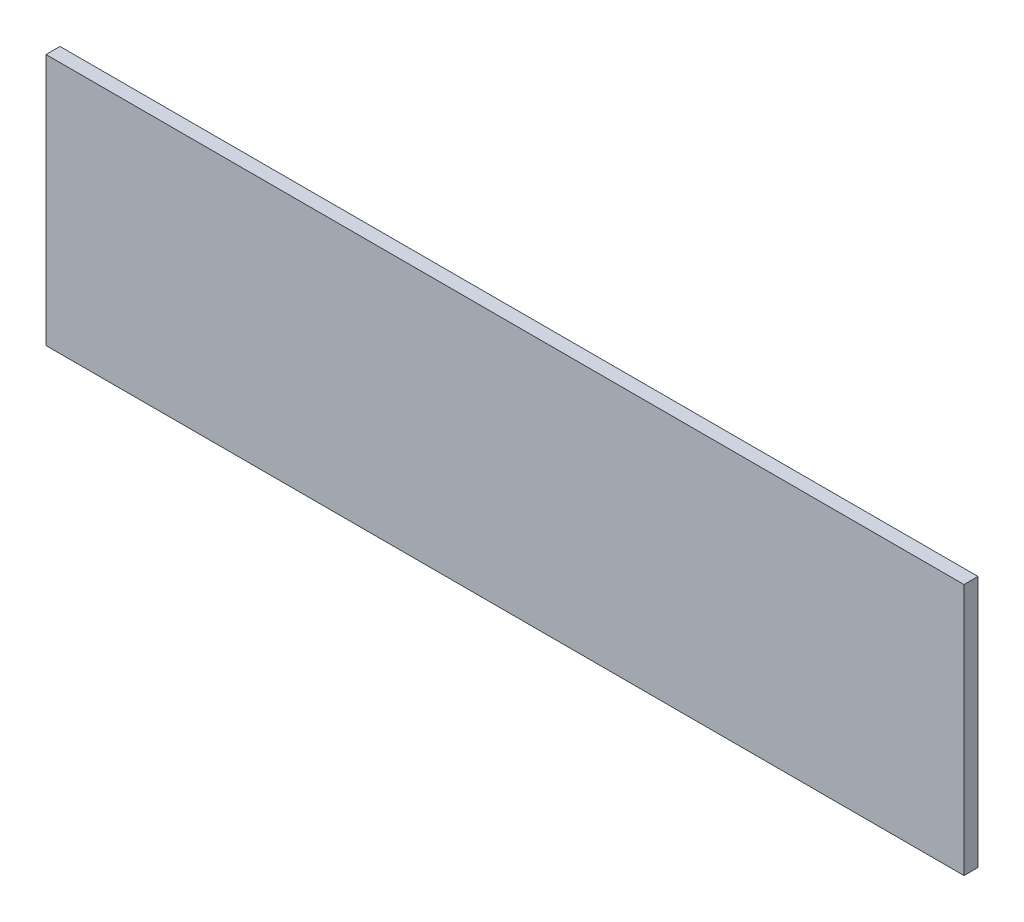
SolidWorks part; units mm, degrees
ref_plane "Front Plane" through (0, 0, 0) normal (0, 0, 1) x (1, 0, 0)
ref_plane "Top Plane" through (0, 0, 0) normal (0, 1, 0) x (1, 0, 0)
ref_plane "Right Plane" through (0, 0, 0) normal (1, 0, 0) x (0, 0, -1)
sketch "Sketch1" plane through (0, 0, 0) normal (0, 0, 1) x (1, 0, 0)
  line L1 (147.5, -40.5) -> (-147.5, -40.5)
  line L2 (147.5, -40.5) -> (147.5, 40.5)
  line L3 (147.5, 40.5) -> (-147.5, 40.5)
  line L4 (-147.5, -40.5) -> (-147.5, 40.5)
  line L5 (147.5, -40.5) -> (-147.5, 40.5) construction
  line L6 (147.5, 40.5) -> (-147.5, -40.5) construction
  point P0 (0, 0)
  dimension "D1" = 295
  dimension "D2" = 81
extrude "Boss-Extrude1" add sketch "Sketch1" along normal blind 4.5
sketch "Sketch2" plane through (0, 0, 4.5) normal (0, 0, 1) x (1, 0, 0)
  line L0 (-147.5, 40.5) -> (-143, 36) construction
  line L1 (-147.5, 40.5) -> (-143, 40.5) construction
  line L2 (-147.5, 40.5) -> (-147.5, 36) construction
  line L3 (-147.5, 36) -> (-143, 36) construction
  line L4 (-143, 40.5) -> (-143, 36) construction
  line L5 (-143, -36) -> (-147.5, -40.5) construction
  line L6 (-147.5, -40.5) -> (-143, -40.5) construction
  line L7 (-147.5, -40.5) -> (-147.5, -36) construction
  line L8 (-147.5, -36) -> (-143, -36) construction
  line L9 (-143, -40.5) -> (-143, -36) construction
  line L10 (143, -36) -> (147.5, -40.5) construction
  line L11 (147.5, -40.5) -> (143, -40.5) construction
  line L12 (147.5, -40.5) -> (147.5, -36) construction
  line L13 (147.5, -36) -> (143, -36) construction
  line L14 (143, -40.5) -> (143, -36) construction
  line L15 (143, 36) -> (147.5, 40.5) construction
  line L16 (147.5, 40.5) -> (143, 40.5) construction
  line L17 (147.5, 40.5) -> (147.5, 36) construction
  line L18 (147.5, 36) -> (143, 36) construction
  line L19 (143, 40.5) -> (143, 36) construction
  circle A0 centre (-145.25, 38.25) radius 1.5
  circle A1 centre (145.25, 38.25) radius 1.5
  circle A2 centre (145.25, -38.25) radius 1.5
  circle A3 centre (-145.25, -38.25) radius 1.5
  circle A4 centre (-145.25, 38.25) radius 3 construction
  dimension "D3" = 4.5
  dimension "D1" = 4.5
  dimension "D2" = 4.5
  dimension "D4" = 4.5
  dimension "D5" = 4.5
  dimension "D6" = 4.5
  dimension "D7" = 4.5
  dimension "D8" = 4.5
extrude "Cut-Extrude1" [suppressed] cut sketch "Sketch2" against normal up to next
